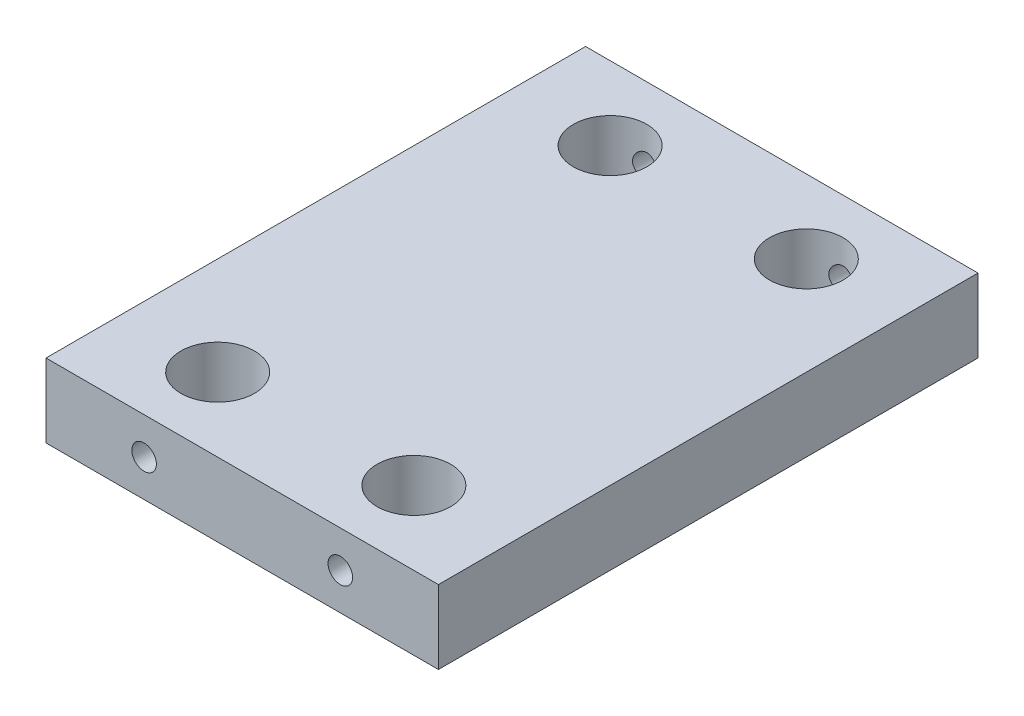
SolidWorks part; units mm, degrees
material "Pine"
ref_plane "Front Plane" through (0, 0, 0) normal (0, 0, 1) x (1, 0, 0)
ref_plane "Top Plane" through (0, 0, 0) normal (0, 1, 0) x (1, 0, 0)
ref_plane "Right Plane" through (0, 0, 0) normal (1, 0, 0) x (0, 0, -1)
sketch "Sketch1" plane through (0, 0, 0) normal (0, 1, 0) x (1, 0, 0)
  line L1 (-50.8, 69.85) -> (50.8, 69.85)
  line L2 (-50.8, 69.85) -> (-50.8, -69.85)
  line L3 (-50.8, -69.85) -> (50.8, -69.85)
  line L4 (50.8, 69.85) -> (50.8, -69.85)
  line L5 (-50.8, 69.85) -> (50.8, -69.85) construction
  line L6 (-50.8, -69.85) -> (50.8, 69.85) construction
  point P0 (0, 0)
  dimension "D1" = 139.7
  dimension "D2" = 101.6
extrude "Boss-Extrude1" add sketch "Sketch1" along normal blind 19.05
hole_wizard "3/4 (0.75) Diameter Hole1" positions "Sketch3" profile "Sketch2" hole size "3/4" standard "Ansi Inch"
sketch "Sketch3" plane through (0, 19.05, 0) normal (0, 1, 0) x (-1, 0, 0)
  line L0 (50.8, -69.85) -> (50.8, 69.85) construction
  line L1 (-50.8, -69.85) -> (50.8, -69.85) construction
  point P0 (25.4, -50.8)
  dimension "D1" = 25.4
  dimension "D2" = 19.05
sketch "Sketch2" plane through (-25.4, 19.05, -50.8) normal (1, 0, 0) x (0, 0, 1)
  line L0 (0, 0) -> (0, 24.7732)
  line L1 (0, 24.7732) -> (9.525, 19.05)
  line L2 (9.525, 19.05) -> (9.525, 0)
  line L5 (9.525, 0) -> (0, 0)
  line L10 (0, 24.7732) -> (-9.525, 19.05) construction
  line L11 (0, -6.35) -> (0, 107.95) construction
  dimension "Hole Dia." = 19.05
  dimension "Hole Depth" = 19.05
  dimension "Drill Angle" = 118
mirror "Mirror1" about plane through (0, 0, 0) normal (0, 0, 1) of "3/4 (0.75) Diameter Hole1"
mirror "Mirror4" about plane through (0, 0, 0) normal (1, 0, 0) of "Mirror1", "3/4 (0.75) Diameter Hole1"
hole_wizard "1/4 (0.25) Diameter Hole1" positions "Sketch5" profile "Sketch4" hole size "1/4" standard "Ansi Inch"
sketch "Sketch5" plane through (0, 0, -69.85) normal (0, 0, -1) x (-1, 0, 0)
  line L0 (-50.8, 19.05) -> (-50.8, 0) construction
  line L1 (-50.8, 0) -> (50.8, 0) construction
  point P0 (-25.4, 9.525)
  dimension "D1" = 25.4
  dimension "D2" = 9.525
sketch "Sketch4" plane through (25.4, 9.525, -69.85) normal (1, 0, 0) x (0, 1, 0)
  line L0 (0, 0) -> (0, 20.9577)
  line L1 (0, 20.9577) -> (3.175, 19.05)
  line L2 (3.175, 19.05) -> (3.175, 0)
  line L5 (3.175, 0) -> (0, 0)
  line L10 (0, 20.9577) -> (-3.175, 19.05) construction
  line L11 (0, -6.35) -> (0, 107.95) construction
  dimension "Hole Dia." = 6.35
  dimension "Hole Depth" = 19.05
  dimension "Drill Angle" = 118
mirror "Mirror5" about plane through (0, 0, 0) normal (0, 0, 1) of "1/4 (0.25) Diameter Hole1"
mirror "Mirror10" about plane through (0, 0, 0) normal (1, 0, 0) of "Mirror5"
